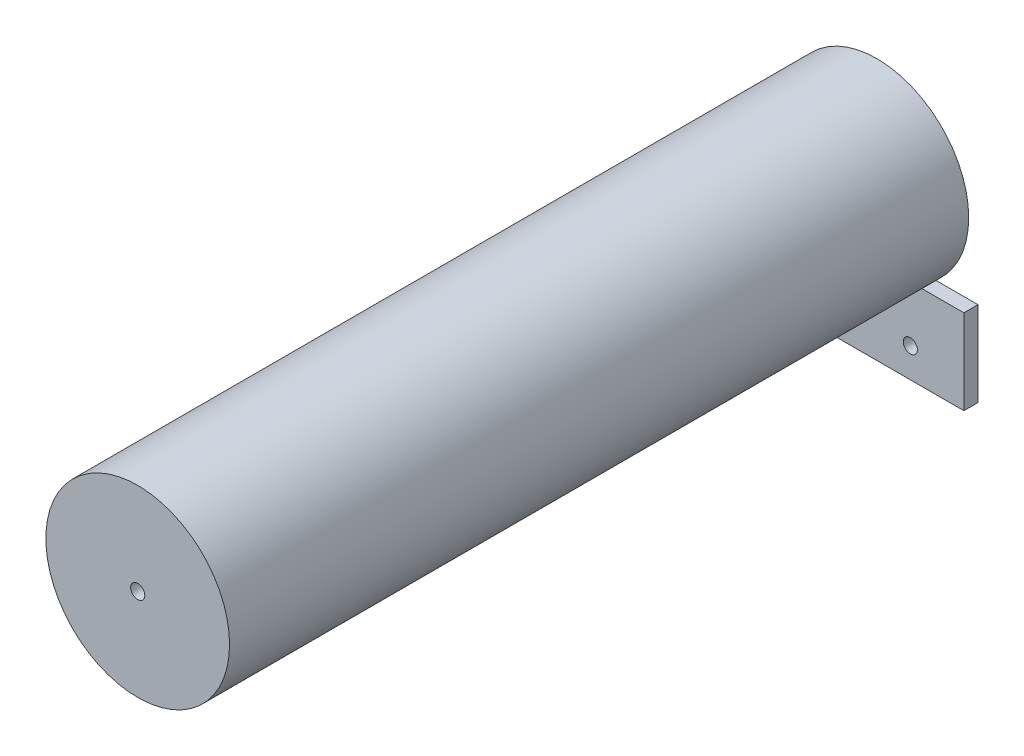
SolidWorks part; units mm, degrees
other "Asse"
other "PiastrinaAsse"
ref_plane "Piano frontale" through (0, 0, 0) normal (0, 0, 1) x (1, 0, 0)
ref_plane "Piano superiore" through (0, 0, 0) normal (0, 1, 0) x (1, 0, 0)
ref_plane "Piano destro" through (0, 0, 0) normal (1, 0, 0) x (0, 0, -1)
sketch "Sketch1" plane through (0, 0, 0) normal (0, 0, 1) x (1, 0, 0)
  circle A0 centre (0, 0) radius 65
  dimension "D1" = 130
extrude "ExtrudeAsse" add sketch "Sketch1" along normal blind 508 and the other way blind 15 contours A0 region at (0, 0, 0)
sketch "Sketch2" plane through (0, 0, 0) normal (0, 1, 0) x (1, 0, 0)
  line L0 (0, 0) -> (0, -508) construction
  line L1 (-65, -508) -> (65, -508) construction
  line L2 (65, -246.5) -> (-65, -246.5) construction
  line L3 (65, -508) -> (65, 15) construction
  line L4 (-65, 15) -> (-65, -508) construction
sketch "Sketch3" plane through (0, 0, 0) normal (1, 0, 0) x (0, 0, -1)
  line L0 (-508, 0) -> (0, 0) construction
  line L1 (-508, 65) -> (-508, -65) construction
  line L2 (-453.833, 10) -> (-190.7071, 10) construction
  line L4 (-353.9249, 10) -> (-358.9249, 12.8868)
  line L5 (-358.9249, 12.8868) -> (-358.9249, 10)
  line L7 (-245, 10) -> (-250, 12.8868)
  line L8 (-250, 12.8868) -> (-250, 0)
  line L9 (-358.9249, 10) -> (-358.9249, -65)
  line L10 (-508, -65) -> (15, -65) construction
  line L11 (-358.9249, -65) -> (-353.9249, -65)
  line L12 (-353.9249, -65) -> (-353.9249, 10)
  line L13 (-250, 0) -> (-250, -65)
  line L14 (-250, -65) -> (-245, -65)
  line L15 (-245, -65) -> (-245, 10)
  line L21 (-142, 10) -> (-142, 12.8868)
  line L22 (-142, 12.8868) -> (-137, 10)
  line L23 (-137, 10) -> (-137, -65)
  line L24 (-137, -65) -> (-142, -65)
  line L25 (-142, -65) -> (-142, 10)
  line L26 (-493, 40.9604) -> (-493, -28.8955) construction
  point P10 (-353.9249, 9.1219)
  dimension "D1" = 10
  dimension "D2" = 5
  dimension "D3" = 142
  dimension "D4" = 30
  dimension "D5" = 5
  dimension "D6" = 5
  dimension "D7" = 250
  dimension "D8" = 30
  dimension "D9" = 358.9249
  dimension "D10" = 15
  dimension "D11" = 30
revolve "Cut-Revolve1" cut sketch "Sketch3" angle 360 about L5 region at (0, -26.7738, 356.4406)
revolve "Cut-Revolve2" cut sketch "Sketch3<3>" angle 360 about L13 region at (0, -26.7738, 247.5157)
sketch "Sketch3<3>" plane through (0, 0, 0) normal (1, 0, 0) x (0, 0, -1) same geometry as "Sketch3"
sketch "Sketch4" plane through (0, 0, 0) normal (1, 0, 0) x (0, 0, -1)
  line L0 (-508, 0) -> (98.5282, 0) construction
  line L1 (-508, 65) -> (-508, -65) construction
  line L7 (-237.7711, -5) -> (-508, -5)
  line L8 (-508, -5) -> (-508, 0)
  line L9 (-508, 0) -> (-237.7711, 0)
  line L10 (-237.7711, -5) -> (-237.7711, 0) construction
  line L11 (-237.7711, -5) -> (-234.8844, 0)
  line L12 (-234.8844, 0) -> (-237.7711, 0)
  dimension "D1" = 30
  dimension "D2" = 5
  dimension "D3" = 270.2289
revolve "Cut-Revolve5" cut sketch "Sketch4" angle 360 about L0 region at (0, -2.4956, 372.1626)
sketch "Sketch5" plane through (0, 0, 0) normal (1, 0, 0) x (0, 0, -1)
  line L3 (15, -65) -> (15, 65) construction
  line L5 (15, -5) -> (15, 0)
  line L7 (-162.1132, 0) -> (-162.1132, -5) construction
  line L8 (15, 0) -> (-313.4256, 0) construction
  line L9 (15, 0) -> (-162.1132, 0)
  line L10 (-162.1132, -5) -> (15, -5)
  line L11 (-165, 0) -> (-162.1132, 0)
  line L12 (-162.1132, -5) -> (-165, 0)
  dimension "D1" = 180
  dimension "D2" = 30
  dimension "D3" = 5
revolve "Cut-Revolve6" cut sketch "Sketch5" angle 360 about L0
revolve "Cut-Revolve7" cut sketch "Sketch3<5>" angle 360 about L25
sketch "Sketch3<5>" plane through (0, 0, 0) normal (1, 0, 0) x (0, 0, -1) same geometry as "Sketch3"
ref_plane "Plane1" through (0, 0, 0) normal (0, 0, -1) x (-1, 0, 0)
sketch "Sketch6" plane through (0, 0, 0) normal (0, 0, -1) x (-1, 0, 0)
  line L1 (54.0154, -45) -> (-71.7504, -45)
  line L2 (54.0154, -45) -> (54.0154, -65)
  line L3 (54.0154, -65) -> (-71.7504, -65)
  line L4 (-71.7504, -45) -> (-71.7504, -65)
  dimension "D1" = 20
extrude "Cut-Extrude1" cut sketch "Sketch6" along normal blind 10
sketch "Sketch7" plane through (0, -45, 0) normal (0, -1, 0) x (1, 0, 0)
  line L0 (0, 0) -> (-76.5739, 0)
  line L1 (-46.9042, 0) -> (46.9042, 0) construction
  line L2 (-76.5739, 0) -> (-76.5739, -10)
  line L3 (-76.5739, -10) -> (0, -10)
  line L4 (0, -10) -> (0, 0)
extrude "ExtrPiastrina" add sketch "Sketch7" along normal blind 60 separate body
sketch "Sketch8" plane through (0, 0, -10) normal (0, 0, -1) x (-1, 0, 0)
  circle A0 centre (38.6927, -84.1313) radius 5
  dimension "D1" = 10
extrude "Foro" cut sketch "Sketch8" against normal up to surface (10 mm away) up to face at (-38.2869, -75, 0)
mirror "Mirror1" about plane through (0, -105, -10) normal (-1, 0, 0) of bodies 115 113
